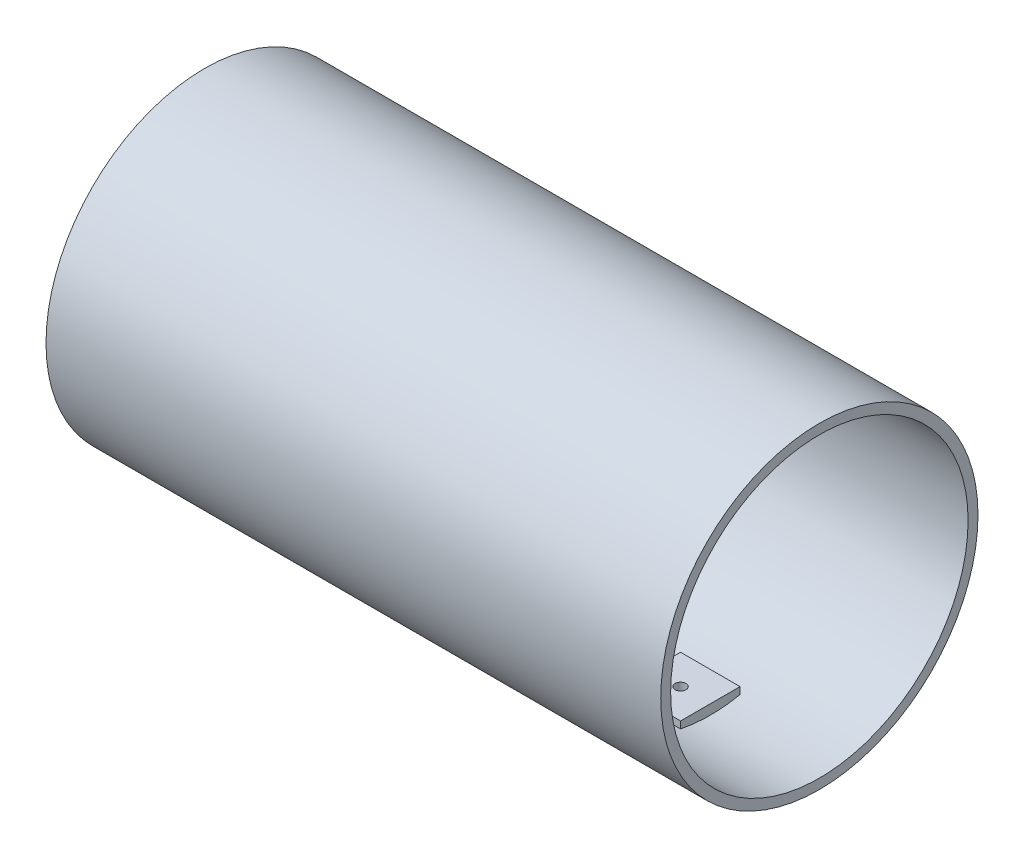
SolidWorks part; units mm, degrees
ref_plane "Ebene vorne" through (0, 0, 0) normal (0, 0, 1) x (1, 0, 0)
ref_plane "Ebene oben" through (0, 0, 0) normal (0, 1, 0) x (1, 0, 0)
ref_plane "Ebene rechts" through (0, 0, 0) normal (1, 0, 0) x (0, 0, -1)
sketch "Skizze1" plane through (0, 0, 0) normal (0, 0, 1) x (1, 0, 0)
  line L0 (0, 0) -> (100, 0) construction
  line L1 (0, 80) -> (310, 80)
  line L2 (0, 80) -> (0, 75)
  line L3 (0, 75) -> (310, 75)
  line L4 (310, 80) -> (310, 75)
  dimension "D1" = 100
  dimension "D2" = 5
  dimension "D3" = 80
  dimension "D4" = 310
revolve "Rotation1" add sketch "Skizze1" angle 360 about L0
ref_plane "Ebene1" through (0, -75, 0) normal (0, 1, 0) x (1, 0, 0)
sketch "Skizze3" plane through (0, 0, 0) normal (0, 1, 0) x (1, 0, 0)
  line L0 (255, -55) -> (275, -55)
  line L2 (215, -55) -> (215, -75)
  line L3 (215, -75) -> (255, -75)
  line L4 (255, -55) -> (255, -75)
  line L5 (195, -45) -> (275, -45)
  line L6 (195, -45) -> (195, -55)
  line L7 (195, -55) -> (215, -55)
  line L8 (275, -45) -> (275, -55)
  line L11 (0, -80) -> (310, -80) construction
  line L12 (310, -80) -> (310, 80) construction
  dimension "D1" = 20
  dimension "D2" = 40
  dimension "D3" = 10
  dimension "D4" = 80
  dimension "D5" = 5
  dimension "D6" = 35
ref_plane "Ebene2" through (0, 0, 75) normal (0, 0, -1) x (-1, 0, 0)
extrude "Aufsatz-Linear austragen1" add sketch "Skizze3" along normal blind 2.5 and the other way blind 2.5 contours L5 L8 L0 L4 L3 L2 L7 L6
sketch "Skizze5" plane through (0, -75, 0) normal (0, 1, 0) x (1, 0, 0)
  line L0 (-88, 0) -> (88, 0) construction
  line L1 (85, -15) -> (55, -15)
  line L2 (85, -15) -> (85, 15)
  line L3 (85, 15) -> (55, 15)
  line L4 (55, -15) -> (55, 15)
  line L5 (85, -15) -> (55, 15) construction
  line L6 (85, 15) -> (55, -15) construction
  line L7 (0, 80) -> (0, -80) construction
  point P0 (70, 0)
  dimension "D1" = 30
  dimension "D2" = 55
extrude "Aufsatz-Linear austragen2" add sketch "Skizze5" along normal blind 5
ref_plane "Ebene3" through (155, 0, 0) normal (-1, 0, 0) x (0, 0, 1)
sketch "Skizze6" plane through (0, -70, 0) normal (0, 1, 0) x (1, 0, 0)
  line L0 (85, 15) -> (55, 15) construction
  line L1 (85, -15) -> (85, 15) construction
  line L2 (55, -15) -> (85, -15) construction
  circle A0 centre (70, 0) radius 15
hole_wizard "Durchgangsloch für M51" positions "Skizze8" profile "Skizze7" hole size "M5" standard "ANSI Metrisch" end condition through all
sketch "Skizze8" plane through (0, -70, 0) normal (0, 1, 0) x (1, 0, 0)
  point P0 (70, 0)
sketch "Skizze7" plane through (70, -70, 0) normal (1, 0, 0) x (0, 0, 1)
  line L0 (0, 0) -> (0, 10)
  line L1 (0, 10) -> (2.75, 10)
  line L2 (2.75, 10) -> (2.75, 0)
  line L5 (2.75, 0) -> (0, 0)
  line L11 (0, -6.35) -> (0, 107.95) construction
  dimension "Bohrerdurchmesser" = 5.5
  dimension "Bohrungstiefe" = 10
mirror "Spiegeln2" about plane through (155, 0, 0) normal (-1, 0, 0) of "Aufsatz-Linear austragen2", "Durchgangsloch für M51"
